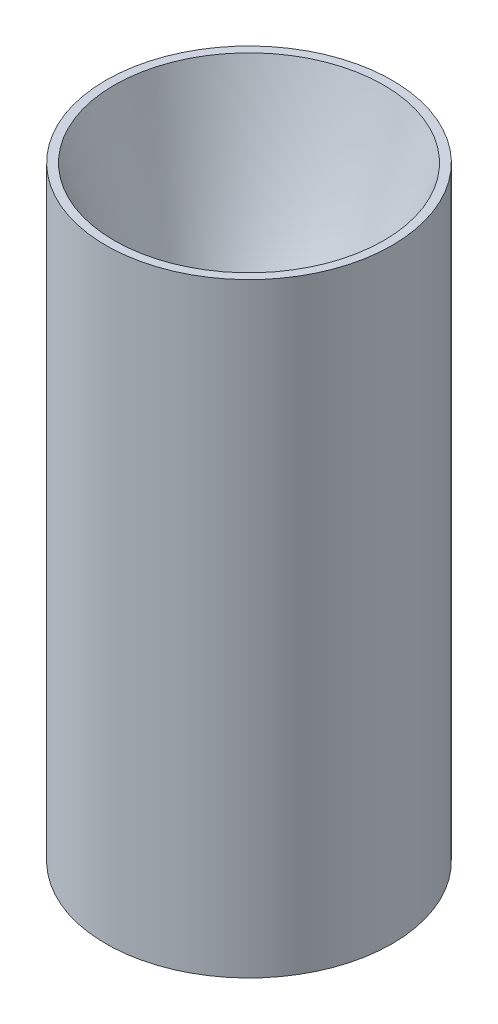
SolidWorks part; units mm, degrees
material "AISI 1020"
ref_plane "Front Plane" through (0, 0, 0) normal (0, 0, 1) x (1, 0, 0)
ref_plane "Top Plane" through (0, 0, 0) normal (0, 1, 0) x (1, 0, 0)
ref_plane "Right Plane" through (0, 0, 0) normal (1, 0, 0) x (0, 0, -1)
sketch "Sketch1" plane through (0, 0, 0) normal (0, 0, 1) x (1, 0, 0)
  line L0 (-0.0055, 165.816) -> (-0.0055, -134.6871) construction
  line L1 (71.7275, 109.9275) -> (76.1945, 109.9275)
  line L4 (53.8815, -59.7275) -> (53.8815, -212.1275)
  line L9 (76.1945, 109.9275) -> (76.1945, -212.1275)
  line L10 (76.1945, -212.1275) -> (53.8815, -212.1275)
  spline S0 degree 2 poles (26.7953, 6.5094) (49.2614, 34.6361) (71.7275, 109.9275) knots 0 0 0 1 1 1 construction
  spline S1 degree 2 poles (26.7953, 6.5094) (49.2614, 34.6361) (71.7275, 109.9275) knots 0 0 0 1 1 1
  spline S2 degree 4 poles (24.1269, -0.7179) (24.126, -0.7018) (24.1243, -0.6738) (24.121, -0.6546) (24.115, -0.5166) (24.1058, -0.4369) (24.0994, -0.1066) (24.0979, 0.0018) (24.102, 0.2678) (24.1085, 0.4272) (24.1205, 0.6469) (24.1414, 0.9016) (24.1752, 1.2027) (24.2265, 1.5422) (24.2905, 1.8812) (24.3671, 2.2165) (24.4563, 2.5494) (24.5577, 2.8783) (24.6716, 3.2035) (24.7972, 3.5238) (24.9353, 3.8398) (25.0841, 4.1494) (25.246, 4.4549) (25.4165, 4.7515) (25.6025, 5.0459) (25.7918, 5.3257) (26.0044, 5.6109) (26.1789, 5.8331) (26.3663, 6.0501) (26.5046, 6.2088) (26.757, 6.4728) (26.837, 6.5526) (27.1016, 6.806) (27.1881, 6.8783) (27.2854, 6.9667) (27.3038, 6.9803) (27.3264, 7.0004) knots 0 0 0 0 0 0.005192 0.010384 0.020768 0.041536 0.082569 0.102427 0.122284 0.142142 0.162 0.201716 0.241431 0.281147 0.320863 0.360578 0.400294 0.44001 0.479725 0.519441 0.559156 0.598872 0.638588 0.678303 0.718019 0.757735 0.79745 0.837166 0.857024 0.876882 0.916597 0.958047 0.979024 0.989512 1 1 1 1 1 construction
  spline S3 degree 4 poles (24.0991, 0.0002) (24.0991, 0.0361) (24.0996, 0.1103) (24.102, 0.2678) (24.1085, 0.4272) (24.1205, 0.6469) (24.1414, 0.9016) (24.1752, 1.2027) (24.2265, 1.5422) (24.2905, 1.8812) (24.3671, 2.2165) (24.4563, 2.5494) (24.5577, 2.8783) (24.6716, 3.2035) (24.7972, 3.5238) (24.9353, 3.8398) (25.0841, 4.1494) (25.246, 4.4549) (25.4165, 4.7515) (25.6025, 5.0459) (25.7918, 5.3257) (26.0044, 5.6109) (26.1789, 5.8331) (26.3663, 6.0501) (26.5046, 6.2088) (26.6704, 6.3823) (26.7445, 6.4586) (26.7953, 6.5094) knots 0.082569 0.082569 0.082569 0.082569 0.082569 0.102427 0.122284 0.142142 0.162 0.201716 0.241431 0.281147 0.320863 0.360578 0.400294 0.44001 0.479725 0.519441 0.559156 0.598872 0.638588 0.678303 0.718019 0.757735 0.79745 0.837166 0.857024 0.876882 0.916597 0.916597 0.916597 0.916597 0.916597
  spline S4 degree 4 poles (24.2082, 2.808) (24.2014, 2.7166) (24.1882, 2.5518) (24.1642, 2.1754) (24.1352, 1.6881) (24.1148, 1.1018) (24.103, 0.6556) (24.0988, 0.1104) (24.0988, -0.0999) (24.102, -0.543) (24.1083, -0.824) (24.1178, -1.1947) (24.1304, -1.5133) (24.1462, -1.8618) (24.1652, -2.1935) (24.1928, -2.6179) (24.2323, -3.1219) (24.3033, -3.8798) (24.4231, -4.8863) (24.5995, -6.0566) (24.8509, -7.385) (25.1518, -8.7034) (25.5018, -10.0095) (25.9004, -11.3017) (26.3469, -12.5779) (26.841, -13.8367) (27.3817, -15.076) (27.9685, -16.2944) (28.6001, -17.4898) (29.2765, -18.6611) (29.9954, -19.8056) (30.758, -20.9237) (31.4592, -21.8743) (32.0887, -22.6733) (32.6241, -23.3203) (33.0723, -23.8398) (33.5085, -24.3297) (33.9358, -24.7883) (34.2456, -25.1137) (34.6121, -25.4859) (34.7661, -25.6398) (35.1509, -26.0187) (35.4776, -26.3286) (35.905, -26.7273) (36.2395, -27.0242) (36.5192, -27.2707) (36.6465, -27.3798) (36.7148, -27.4387) (36.7496, -27.4686) knots 0 0 0 0 0 0.010393 0.020785 0.041571 0.062104 0.072371 0.082638 0.092575 0.102512 0.112449 0.122387 0.132324 0.142261 0.152198 0.162135 0.18201 0.201884 0.241633 0.281382 0.32113 0.360879 0.400628 0.440377 0.480126 0.519874 0.559623 0.599372 0.639121 0.67887 0.718618 0.758367 0.798116 0.81799 0.837865 0.857739 0.877613 0.897488 0.907425 0.917362 0.927629 0.937896 0.958429 0.979215 0.989607 0.994804 1 1 1 1 1 construction
  spline S5 degree 4 poles (24.0991, 0.0002) (24.0991, -0.0704) (24.0996, -0.2134) (24.102, -0.543) (24.1083, -0.824) (24.1178, -1.1947) (24.1304, -1.5133) (24.1462, -1.8618) (24.1652, -2.1935) (24.1928, -2.6179) (24.2323, -3.1219) (24.3033, -3.8798) (24.4231, -4.8863) (24.5995, -6.0566) (24.8509, -7.385) (25.1518, -8.7034) (25.5018, -10.0095) (25.9004, -11.3017) (26.3469, -12.5779) (26.841, -13.8367) (27.3817, -15.076) (27.9685, -16.2944) (28.6001, -17.4898) (29.2765, -18.6611) (29.9954, -19.8056) (30.758, -20.9237) (31.4592, -21.8743) (32.0887, -22.6733) (32.6241, -23.3203) (33.0723, -23.8398) (33.5085, -24.3297) (33.9358, -24.7883) (34.2456, -25.1137) (34.5369, -25.4095) (34.6364, -25.5098) (34.6863, -25.5597) knots 0.082638 0.082638 0.082638 0.082638 0.082638 0.092575 0.102512 0.112449 0.122387 0.132324 0.142261 0.152198 0.162135 0.18201 0.201884 0.241633 0.281382 0.32113 0.360879 0.400628 0.440377 0.480126 0.519874 0.559623 0.599372 0.639121 0.67887 0.718618 0.758367 0.798116 0.81799 0.837865 0.857739 0.877613 0.897488 0.907425 0.917362 0.917362 0.917362 0.917362 0.917362
  spline S6 degree 1 poles (34.6863, -25.5597) (43.2939, -34.1673) knots 0 0 1 1 construction
  spline S7 degree 1 poles (34.6863, -25.5597) (43.2939, -34.1673) knots 0 0 1 1
  spline S8 degree 4 poles (53.7724, -62.5352) (53.7792, -62.4464) (53.7924, -62.2737) (53.8104, -62.0016) (53.8309, -61.6599) (53.848, -61.2921) (53.8616, -60.9658) (53.8717, -60.5752) (53.8784, -60.2939) (53.8818, -59.8332) (53.8818, -59.6304) (53.8786, -59.1816) (53.8723, -58.9048) (53.8628, -58.5326) (53.8502, -58.2128) (53.8304, -57.7816) (53.8004, -57.281) (53.7562, -56.688) (53.6773, -55.8485) (53.5774, -55.0082) (53.4567, -54.1724) (53.2868, -53.1724) (53.0921, -52.1774) (52.8664, -51.1885) (52.61, -50.2075) (52.3293, -49.2331) (52.0243, -48.266) (51.6335, -47.1491) (51.1395, -45.8904) (50.5987, -44.651) (50.0121, -43.4327) (49.3801, -42.2371) (48.7041, -41.0662) (47.9845, -39.921) (47.2231, -38.8041) (46.5199, -37.8515) (45.8935, -37.0557) (45.3528, -36.4034) (44.9151, -35.8942) (44.5148, -35.447) (44.1815, -35.0846) (43.8739, -34.7603) (43.6741, -34.5515) (43.3653, -34.2383) (43.2159, -34.0889) (42.8277, -33.7066) (42.5041, -33.3998) (42.0741, -32.9986) (41.7412, -32.7033) (41.4607, -32.4559) (41.3338, -32.3472) (41.2653, -32.2883) (41.2305, -32.2583) knots 0 0 0 0 0 0.010393 0.020785 0.031178 0.041571 0.051838 0.062104 0.072371 0.082638 0.092575 0.102512 0.112449 0.122387 0.132324 0.142261 0.162135 0.18201 0.201884 0.241633 0.261507 0.281382 0.32113 0.360879 0.380754 0.400628 0.440377 0.480126 0.519874 0.559623 0.599372 0.639121 0.67887 0.718618 0.758367 0.798116 0.81799 0.837865 0.857739 0.877613 0.887551 0.897488 0.907425 0.917362 0.927629 0.937896 0.958429 0.979215 0.989607 0.994804 1 1 1 1 1 construction
  spline S9 degree 4 poles (53.8815, -59.7275) (53.8815, -59.657) (53.881, -59.5154) (53.8786, -59.1816) (53.8723, -58.9048) (53.8628, -58.5326) (53.8502, -58.2128) (53.8304, -57.7816) (53.8004, -57.281) (53.7562, -56.688) (53.6773, -55.8485) (53.5774, -55.0082) (53.4567, -54.1724) (53.2868, -53.1724) (53.0921, -52.1774) (52.8664, -51.1885) (52.61, -50.2075) (52.3293, -49.2331) (52.0243, -48.266) (51.6335, -47.1491) (51.1395, -45.8904) (50.5987, -44.651) (50.0121, -43.4327) (49.3801, -42.2371) (48.7041, -41.0662) (47.9845, -39.921) (47.2231, -38.8041) (46.5199, -37.8515) (45.8935, -37.0557) (45.3528, -36.4034) (44.9151, -35.8942) (44.5148, -35.447) (44.1815, -35.0846) (43.8739, -34.7603) (43.6741, -34.5515) (43.4444, -34.3185) (43.3438, -34.2172) (43.2939, -34.1673) knots 0.082638 0.082638 0.082638 0.082638 0.082638 0.092575 0.102512 0.112449 0.122387 0.132324 0.142261 0.162135 0.18201 0.201884 0.241633 0.261507 0.281382 0.32113 0.360879 0.380754 0.400628 0.440377 0.480126 0.519874 0.559623 0.599372 0.639121 0.67887 0.718618 0.758367 0.798116 0.81799 0.837865 0.857739 0.877613 0.887551 0.897488 0.907425 0.917362 0.917362 0.917362 0.917362 0.917362
  spline S10 degree 2 poles (36.8348, 6.4922) (58.6412, 42.997) (81.7275, 109.9275) knots 0.283015 0.283015 0.283015 0.999243 0.999243 0.999243 construction
  dimension "D1" = 24.1046
  dimension "D2" = 53.8871
  dimension "D3" = 152.4
  dimension "D4" = 322.055
  dimension "D5" = 152.4
  dimension "D7" = 24.0991
  dimension "D8" = 26.7953
  dimension "D9" = 34.6863
  dimension "D10" = 0.0002
revolve "Revolve2" add sketch "Sketch1" angle 360 about L0
sketch "Sketch2" plane through (0, -212.1275, 0) normal (0, -1, 0) x (1, 0, 0)
  line L1 (65.2, 0) -> (65.2, -54.0399) construction
  circle A3 centre (0, 0) radius 65.2 construction
  dimension "D1" = 130.4
hole_wizard "3/8-24 Tapped Hole1" positions "Sketch3" profile "Sketch4" tap size "3/8-24" standard "ANSI Inch"
sketch "Sketch3" plane through (0, -212.1275, 0) normal (0, -1, 0) x (-1, 0, 0)
  point P0 (-65.2, 0)
sketch "Sketch4" plane through (65.2, -212.1275, 0) normal (1, 0, 0) x (0, 0, -1)
  line L0 (0, 0) -> (0, 27.5335)
  line L1 (0, 27.5335) -> (4.2164, 25)
  line L2 (4.2164, 25) -> (4.2164, 0)
  line L5 (4.2164, 0) -> (0, 0)
  line L10 (0, 27.5335) -> (-4.2164, 25) construction
  line L11 (0, -6.35) -> (0, 107.95) construction
  dimension "Tap Drill Dia." = 8.4328
  dimension "Tap Drill Depth" = 25
  dimension "Drill Angle" = 118
cosmetic thread "Hole Thread1" parameters "D1"=20, "D2"=9.525
sketch "Sketch5" plane through (0, 0, 0) normal (0, 0, 1) x (1, 0, 0)
  line L0 (0, -228.487) -> (-0.0055, 109.9275) construction
  line L1 (71.7275, 109.9275) -> (-71.7386, 109.9275) construction
pattern_circular "CirPattern1" count 8 over 360 about axis through (0, -228.487, 0) along (0, 1, 0) of "3/8-24 Tapped Hole1"
cosmetic thread "Hole Thread2" parameters "D1"=20, "D2"=9.525
cosmetic thread "Hole Thread3" parameters "D1"=20, "D2"=9.525
cosmetic thread "Hole Thread4" parameters "D1"=20, "D2"=9.525
cosmetic thread "Hole Thread5" parameters "D1"=20, "D2"=9.525
cosmetic thread "Hole Thread6" parameters "D1"=20, "D2"=9.525
cosmetic thread "Hole Thread7" parameters "D1"=20, "D2"=9.525
cosmetic thread "Hole Thread8" parameters "D1"=20, "D2"=9.525
sketch "Sketch8" plane through (0, -212.1275, 0) normal (0, -1, 0) x (1, 0, 0)
  circle A0 centre (0, 0) radius 53.8815 construction
  circle A1 centre (0, 0) radius 76.49 construction
  circle A2 centre (0, 0) radius 65.2002 construction
  dimension "D1" = 107.7631
  dimension "D2" = 130.4004
  dimension "D3" = 152.98
sketch "Sketch9" plane through (0, -212.1275, 0) normal (0, -1, 0) x (1, 0, 0)
  circle A0 centre (0, 0) radius 53.8815
  circle A1 centre (0, 0) radius 56.8815
  dimension "D1" = 3
extrude "Cut-Extrude1" [suppressed] cut sketch "Sketch9" against normal blind 6
